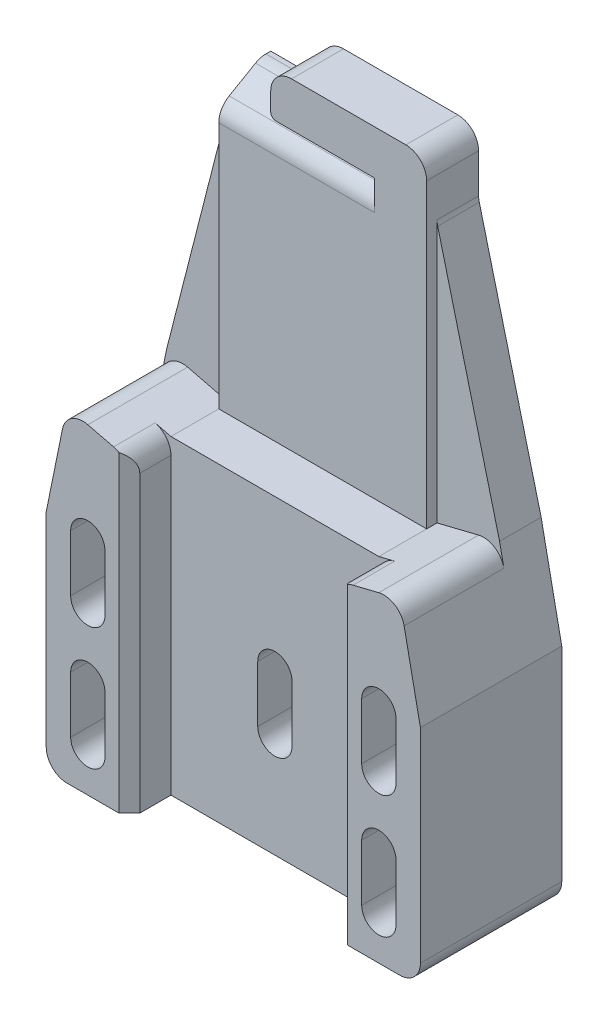
SolidWorks part; units mm, degrees
ref_plane "Front Plane" through (0, 0, 0) normal (0, 0, 1) x (1, 0, 0)
ref_plane "Top Plane" through (0, 0, 0) normal (0, 1, 0) x (1, 0, 0)
ref_plane "Right Plane" through (0, 0, 0) normal (1, 0, 0) x (0, 0, -1)
sketch "Sketch1" plane through (0, 0, 0) normal (0, 0, 1) x (1, 0, 0)
  line L0 (0, 0) -> (10, 0) construction
  line L1 (0, 0) -> (0, 10) construction
  line L2 (-143.3708, 41.2466) -> (77.8135, -51.9066) construction
  line L3 (74.9025, -58.8186) -> (-146.2818, 34.3346) construction
  line L4 (71.9914, -65.7306) -> (-149.1928, 27.4226) construction
  line L5 (-143.3708, 41.2466) -> (77.8135, -51.9066) construction
  line L6 (74.9025, -58.8186) -> (-146.2818, 34.3346) construction
  line L7 (71.9914, -65.7306) -> (-149.1928, 27.4226) construction
  line L8 (5, 15) -> (-5, 15) construction
  line L9 (-5, 16) -> (5, 16) construction
  line L10 (5, 16) -> (5, 15) construction
  line L11 (-5, 15) -> (-5, 16) construction
  line L12 (12.35, -30.4565) -> (12.35, -35.8818) construction
  line L13 (15.65, -35.8818) -> (15.65, -30.4565) construction
  line L14 (1.65, -24.5603) -> (1.65, -29.9856) construction
  line L15 (-1.65, -29.9856) -> (-1.65, -24.5603) construction
  line L16 (-12.35, -24.0894) -> (-12.35, -18.6641) construction
  line L17 (-15.65, -18.6641) -> (-15.65, -24.0894) construction
  line L18 (5, 15) -> (-5, 15) construction
  line L19 (-5, 16) -> (5, 16) construction
  line L20 (5, 16) -> (5, 15) construction
  line L21 (-5, 15) -> (-5, 16) construction
  line L22 (12.35, -30.4565) -> (12.35, -35.8818)
  line L23 (15.65, -35.8818) -> (15.65, -30.4565)
  line L24 (1.65, -24.5603) -> (1.65, -29.9856) construction
  line L25 (-1.65, -29.9856) -> (-1.65, -24.5603) construction
  line L26 (-12.35, -24.0894) -> (-12.35, -18.6641)
  line L27 (-15.65, -18.6641) -> (-15.65, -24.0894)
  line L28 (0, 0) -> (0, -35.411) construction
  line L29 (-15.65, -35.8818) -> (-15.65, -30.4565)
  line L30 (-12.35, -30.4565) -> (-12.35, -35.8818)
  line L31 (15.65, -18.6641) -> (15.65, -24.0894)
  line L32 (12.35, -24.0894) -> (12.35, -18.6641)
  line L33 (143.3708, 41.2466) -> (-77.8135, -51.9066) construction
  line L34 (-74.9025, -58.8186) -> (146.2818, 34.3346) construction
  line L35 (-71.9914, -65.7306) -> (149.1928, 27.4226) construction
  circle A0 centre (0, 0) radius 10 construction
  circle A1 centre (0, 0) radius 10 construction
  circle A2 centre (0, 72.5) radius 82.5 construction
  circle A3 centre (0, 72.5) radius 82.5 construction
  arc A4 (15.65, -30.4565) -> (12.35, -30.4565) centre (14, -30.4565) ccw construction
  arc A5 (12.35, -35.8818) -> (15.65, -35.8818) centre (14, -35.8818) ccw construction
  arc A6 (-1.65, -29.9856) -> (1.65, -29.9856) centre (0, -29.9856) ccw construction
  arc A7 (1.65, -24.5603) -> (-1.65, -24.5603) centre (0, -24.5603) ccw construction
  arc A8 (-15.65, -24.0894) -> (-12.35, -24.0894) centre (-14, -24.0894) ccw construction
  arc A9 (-12.35, -18.6641) -> (-15.65, -18.6641) centre (-14, -18.6641) ccw construction
  circle A10 centre (-14, -18.6641) radius 4 construction
  circle A11 centre (0, -24.5603) radius 4 construction
  circle A12 centre (14, -30.4565) radius 4 construction
  arc A13 (15.65, -30.4565) -> (12.35, -30.4565) centre (14, -30.4565) ccw
  arc A14 (12.35, -35.8818) -> (15.65, -35.8818) centre (14, -35.8818) ccw
  arc A15 (-1.65, -29.9856) -> (1.65, -29.9856) centre (0, -29.9856) ccw construction
  arc A16 (1.65, -24.5603) -> (-1.65, -24.5603) centre (0, -24.5603) ccw construction
  arc A17 (-15.65, -24.0894) -> (-12.35, -24.0894) centre (-14, -24.0894) ccw
  arc A18 (-12.35, -18.6641) -> (-15.65, -18.6641) centre (-14, -18.6641) ccw
  circle A19 centre (-14, -18.6641) radius 4 construction
  circle A20 centre (0, -24.5603) radius 4 construction
  circle A21 centre (14, -30.4565) radius 4 construction
  circle A22 centre (-14, -30.4565) radius 4 construction
  arc A23 (-12.35, -35.8818) -> (-15.65, -35.8818) centre (-14, -35.8818) cw
  arc A24 (-15.65, -30.4565) -> (-12.35, -30.4565) centre (-14, -30.4565) cw
  arc A25 (12.35, -18.6641) -> (15.65, -18.6641) centre (14, -18.6641) cw
  arc A26 (15.65, -24.0894) -> (12.35, -24.0894) centre (14, -24.0894) cw
  circle A27 centre (14, -18.6641) radius 4 construction
  dimension "D1" = 20
sketch "Sketch2" plane through (0, 0, 0) normal (0, 0, 1) x (1, 0, 0)
  line L0 (10, 21) -> (23.5124, -45.3134) construction
  line L1 (-18, -39.8818) -> (-18, -18.2607)
  line L2 (-19.7958, -27.0738) -> (-10, 21) construction
  line L3 (-10, 21) -> (10, 21) construction
  line L4 (10, 21) -> (22.4056, -39.8818) construction
  line L5 (22.4056, -39.8818) -> (-22.4056, -39.8818) construction
  line L6 (-22.4056, -39.8818) -> (-10, 21) construction
  line L7 (-10, 21) -> (10, 21)
  line L8 (0, -39.8818) -> (0, 21) construction
  line L9 (10, 21) -> (10, -10) construction
  line L10 (10, -10) -> (-10, -10) construction
  line L11 (-10, -10) -> (-10, 21) construction
  line L12 (10, -10) -> (16.0152, -8.52) construction
  line L13 (-10, -10) -> (-16.0152, -8.52) construction
  line L14 (-12.35, -24.0894) -> (-12.35, -18.6641) construction
  line L15 (-15.65, -18.6641) -> (-15.65, -24.0894) construction
  line L16 (-1.65, -29.9856) -> (-1.65, -24.5603) construction
  line L17 (1.65, -24.5603) -> (1.65, -29.9856) construction
  line L18 (12.35, -30.4565) -> (12.35, -35.8818) construction
  line L19 (15.65, -35.8818) -> (15.65, -30.4565) construction
  line L20 (-12.35, -24.0894) -> (-12.35, -18.6641)
  line L21 (-15.65, -18.6641) -> (-15.65, -24.0894)
  line L22 (-1.65, -29.9856) -> (-1.65, -24.5603)
  line L23 (1.65, -24.5603) -> (1.65, -29.9856)
  line L24 (12.35, -30.4565) -> (12.35, -35.8818)
  line L25 (15.65, -35.8818) -> (15.65, -30.4565)
  line L26 (-19.7958, -27.0738) -> (23.5124, -45.3134) construction
  line L27 (19.7958, -27.0738) -> (-23.5124, -45.3134) construction
  line L28 (-71.9914, -65.7306) -> (149.1928, 27.4226) construction
  line L29 (71.9914, -65.7306) -> (-149.1928, 27.4226) construction
  line L30 (-12.35, -30.4565) -> (-12.35, -35.8818) construction
  line L31 (-15.65, -35.8818) -> (-15.65, -30.4565) construction
  line L32 (-12.35, -30.4565) -> (-12.35, -35.8818)
  line L33 (-15.65, -35.8818) -> (-15.65, -30.4565)
  line L34 (12.35, -24.0894) -> (12.35, -18.6641) construction
  line L35 (15.65, -18.6641) -> (15.65, -24.0894) construction
  line L36 (12.35, -24.0894) -> (12.35, -18.6641)
  line L37 (15.65, -18.6641) -> (15.65, -24.0894)
  line L38 (18, -39.8818) -> (18, -18.2607)
  line L39 (-18, -18.2607) -> (-10, 21)
  line L40 (10, 21) -> (18, -18.2607)
  line L41 (18, -39.8818) -> (-18, -39.8818)
  circle A0 centre (0, 0) radius 10 construction
  circle A1 centre (0, 0) radius 10 construction
  circle A2 centre (0, 72.5) radius 82.5 construction
  arc A3 (-15.65, -24.0894) -> (-12.35, -24.0894) centre (-14, -24.0894) ccw construction
  arc A4 (-12.35, -18.6641) -> (-15.65, -18.6641) centre (-14, -18.6641) ccw construction
  arc A5 (1.65, -24.5603) -> (-1.65, -24.5603) centre (0, -24.5603) ccw construction
  arc A6 (-1.65, -29.9856) -> (1.65, -29.9856) centre (0, -29.9856) ccw construction
  arc A7 (12.35, -35.8818) -> (15.65, -35.8818) centre (14, -35.8818) ccw construction
  arc A8 (15.65, -30.4565) -> (12.35, -30.4565) centre (14, -30.4565) ccw construction
  arc A9 (-15.65, -24.0894) -> (-12.35, -24.0894) centre (-14, -24.0894) ccw
  arc A10 (-12.35, -18.6641) -> (-15.65, -18.6641) centre (-14, -18.6641) ccw
  arc A11 (1.65, -24.5603) -> (-1.65, -24.5603) centre (0, -24.5603) ccw
  arc A12 (-1.65, -29.9856) -> (1.65, -29.9856) centre (0, -29.9856) ccw
  arc A13 (12.35, -35.8818) -> (15.65, -35.8818) centre (14, -35.8818) ccw
  arc A14 (15.65, -30.4565) -> (12.35, -30.4565) centre (14, -30.4565) ccw
  arc A15 (-12.35, -30.4565) -> (-15.65, -30.4565) centre (-14, -30.4565) ccw construction
  arc A16 (-15.65, -35.8818) -> (-12.35, -35.8818) centre (-14, -35.8818) ccw construction
  arc A17 (-12.35, -30.4565) -> (-15.65, -30.4565) centre (-14, -30.4565) ccw
  arc A18 (-15.65, -35.8818) -> (-12.35, -35.8818) centre (-14, -35.8818) ccw
  arc A19 (15.65, -18.6641) -> (12.35, -18.6641) centre (14, -18.6641) ccw construction
  arc A20 (12.35, -24.0894) -> (15.65, -24.0894) centre (14, -24.0894) ccw construction
  arc A21 (15.65, -18.6641) -> (12.35, -18.6641) centre (14, -18.6641) ccw
  arc A22 (12.35, -24.0894) -> (15.65, -24.0894) centre (14, -24.0894) ccw
  circle A23 centre (-14, -18.6641) radius 4 construction
  circle A24 centre (-14, -18.6641) radius 4 construction
  circle A25 centre (-14, -35.8818) radius 4 construction
sketch "Sketch3" plane through (0, 0, 0) normal (1, 0, 0) x (0, 0, -1)
  line L0 (0, 21) -> (0, -39.8818) construction
  line L1 (0, -39.8818) -> (-13.6002, -39.8818) construction
  line L2 (-13.6002, -39.8818) -> (-13.6002, 21) construction
  line L3 (-13.6002, 21) -> (0, 21) construction
  line L4 (-5, 21) -> (-5, -10)
  line L5 (-5, -10) -> (-9.6002, -10)
  line L6 (-9.6002, -10) -> (-9.6002, -39.8818)
  line L7 (-9.6002, -39.8818) -> (0, -39.8818)
  line L8 (0, -10) -> (-13.6002, -10) construction
  line L11 (-10.7004, -10) -> (-10.7004, 21) construction
  line L12 (-6.6002, -10) -> (-6.6002, 21) construction
  line L13 (-9.1002, -10) -> (-9.1002, 21) construction
  line L14 (-10.7004, 5.5) -> (-9.1002, 5.5) construction
  line L15 (-6.6002, 5.5) -> (-5, 5.5) construction
  line L16 (-7.1002, 21) -> (-7.1002, -10) construction
  line L17 (-5, 21) -> (0, 21)
  line L18 (0, 21) -> (0, -39.8818)
  dimension "D1" = 5
  dimension "D2" = 1.6002
  dimension "D3" = 0.5
  dimension "D4" = 2
  dimension "D5" = 0.5
  dimension "D6" = 4
extrude "Boss-Extrude1" add sketch "Sketch2" along normal up to vertex (13.6002 mm away) up to point (0, 21, 13.6002)
sketch "Sketch4" plane through (0, 0, 13.6002) normal (0, 0, 1) x (1, 0, 0)
  line L0 (-22.4056, -39.8818) -> (-10, 21) construction
  line L1 (-10, 21) -> (10, 21) construction
  line L2 (10, 21) -> (22.4056, -39.8818) construction
  line L3 (-16.0152, -8.52) -> (-10, 21)
  line L4 (-10, 21) -> (10, 21)
  line L5 (10, 21) -> (16.0152, -8.52)
  line L6 (10, -10) -> (-10, -10) construction
  line L7 (10, -10) -> (-10, -10)
  line L8 (10, -10) -> (16.0152, -8.52) construction
  line L9 (10, -10) -> (16.0152, -8.52)
  line L10 (-10, -10) -> (-16.0152, -8.52) construction
  line L11 (-10, -10) -> (-16.0152, -8.52)
extrude "Cut-Extrude1" cut sketch "Sketch4" against normal up to vertex (8.6002 mm away) up to point (0, 21, 5)
sketch "Sketch5" plane through (0, 0, 5) normal (0, 0, 1) x (1, 0, 0)
  line L0 (-10, -10) -> (-16.0152, -8.52)
  line L1 (-16.0152, -8.52) -> (-10, 21)
  line L2 (-10, 21) -> (-10, -10)
  line L3 (16.0152, -8.52) -> (10, -10)
  line L4 (10, -10) -> (10, 21)
  line L5 (10, 21) -> (16.0152, -8.52)
  line L6 (10, 21) -> (22.4056, -39.8818) construction
  line L7 (10, -10) -> (16.0152, -8.52) construction
  line L8 (-10, -10) -> (-16.0152, -8.52) construction
  line L9 (-10, -10) -> (-10, 21) construction
  line L10 (-22.4056, -39.8818) -> (-10, 21) construction
  line L11 (10, 21) -> (10, -10) construction
extrude "Cut-Extrude2" cut sketch "Sketch5" against normal blind 1
sketch "Sketch6" plane through (0, 0, 5) normal (0, 0, 1) x (1, 0, 0)
  line L0 (-16.0152, -8.52) -> (-10, 21) construction
  line L1 (10, 21) -> (16.0152, -8.52) construction
  line L2 (-16.0152, -8.52) -> (-10, 21)
  line L3 (10, 21) -> (16.0152, -8.52)
  line L4 (10, -10) -> (10, 21) construction
  line L5 (-10, 21) -> (-10, -10) construction
  line L6 (10, 15) -> (10, 21)
  line L7 (-10, 21) -> (-10, 15)
  line L8 (10, 15) -> (-10, 15) construction
  line L9 (5, 15) -> (-5, 15) construction
  line L10 (16.0152, -8.52) -> (10, 15)
  line L11 (-10, 15) -> (-16.0152, -8.52)
extrude "Cut-Extrude3" cut sketch "Sketch6" against normal through all
sketch "Sketch7" plane through (0, 0, 13.6002) normal (0, 0, 1) x (1, 0, 0)
  line L0 (22.4056, -39.8818) -> (-22.4056, -39.8818) construction
  line L1 (10, -39.8818) -> (-10, -39.8818)
  line L2 (-10, 21) -> (10, 21) construction
  line L3 (-10, 21) -> (10, 21)
  line L4 (10, 21) -> (10, -39.8818)
  line L5 (-10, 21) -> (-10, -39.8818)
  line L6 (10, 21) -> (10, -10) construction
  line L7 (-10, -10) -> (-10, 21) construction
extrude "Cut-Extrude4" cut sketch "Sketch7" against normal up to vertex (4 mm away) up to point (0, -10, 9.6002)
sketch "Sketch8" plane through (0, 0, 0) normal (1, 0, 0) x (0, 0, -1)
  line L0 (0, 15) -> (-5, 15) construction
  line L1 (0, 21) -> (0, -39.8818) construction
  line L2 (0, 16) -> (-5, 16) construction
  line L3 (-5, 21) -> (-5, -10) construction
  line L4 (-5, 21) -> (0, 21) construction
  line L5 (-5, 21) -> (-5, -10) construction
  line L6 (0, 21) -> (0, -39.8818) construction
  line L7 (-5, 21) -> (0, 21) construction
  line L8 (-5, 15) -> (-1, 17.3094)
  line L9 (-1, 17.3094) -> (0, 17.3094)
  line L10 (-5, 16.1547) -> (0, 19.0415) construction
  line L11 (-4, 16.7321) -> (-5, 16.7321)
  line L12 (0, 19.0415) -> (0, 17.3094)
  line L13 (-4, 16.7321) -> (0, 19.0415)
  line L14 (-5, 15) -> (-5, 16.7321)
  dimension "D1" = 1
  dimension "D2" = 1
  dimension "D3" = 30
extrude "Cut-Extrude5" cut sketch "Sketch8" along normal up to vertex (5 mm away) and the other way through all up to point (5, 15, 0)
sketch "Sketch9" plane through (-10, 0, 0) normal (-1, 0, 0) x (0, 0, 1)
  line L4 (0, 19.0415) -> (4, 16.7321)
  line L5 (5, 16.7321) -> (5, 21)
  line L6 (5, 21) -> (0, 21)
  line L7 (0, 21) -> (0, 19.0415)
  line L8 (0, 19.0415) -> (4, 16.7321)
  line L9 (5, 16.7321) -> (5, 21)
  line L10 (5, 21) -> (0, 21)
  line L11 (0, 21) -> (0, 19.0415)
  line L13 (4, 16.7321) -> (5, 16.7321)
  line L14 (4, 16.7321) -> (5, 16.7321)
  dimension "D1" = 0
extrude "Cut-Extrude6" cut sketch "Sketch9" against normal up to vertex (5 mm away) up to point (-5, 16, 0)
chamfer "Chamfer1" distance 1 angle 45 2 edges at (-10, -24.9409, 13.6002) (10, -24.9409, 13.6002)
fillet "Fillet1" radius 2 8 edges at (10, 15, 2) (-10, 15, 2) (-5, 21, 2.5) (10, 21, 2.5) (-10, -10, 11.1002) (10, -10, 11.1002) (18, -39.8818, 6.8001) (-18, -39.8818, 6.8001)
fillet "Fillet2" radius 2 3 edges at (-2.5, 15, 5) (0, 16.7321, 4) (-2.5, 17.3094, 1)
fillet "Fillet3" radius 0.5 4 edges at (-4.9999, 19.0207, 0.0359) (-5, 16.7321, 4.7679) (-5, 16.8002, 4.0183) (-5, 18, 1.8038)
sketch "Sketch10" plane through (0, 0, 13.6002) normal (0, 0, 1) x (1, 0, 0)
  line L1 (-16.0152, -8.52) -> (-11.5222, -9.6255) construction
  line L2 (-16.0152, -8.52) -> (-16.4309, -10.5602)
  line L3 (-16.0152, -8.52) -> (-13.9933, -9.0175)
  line L5 (11.5222, -9.6255) -> (16.0152, -8.52) construction
  line L6 (16.4309, -10.5602) -> (16.0152, -8.52)
  line L7 (13.9933, -9.0175) -> (16.0152, -8.52)
  line L8 (-22.4056, -39.8818) -> (-10, 21) construction
  line L9 (10, 21) -> (22.4056, -39.8818) construction
  line L10 (11.5222, -9.6255) -> (16.0152, -8.52) construction
  arc A0 (16.4309, -10.5602) -> (13.9933, -9.0175) centre (14.4712, -10.9596) ccw
  arc A1 (-13.9933, -9.0175) -> (-16.4309, -10.5602) centre (-14.4712, -10.9596) ccw
  dimension "D1" = 2
extrude "Cut-Extrude7" cut sketch "Sketch10" against normal up to surface (9.6002 mm away) up to face at (11.5155, 2.8715, 4)
